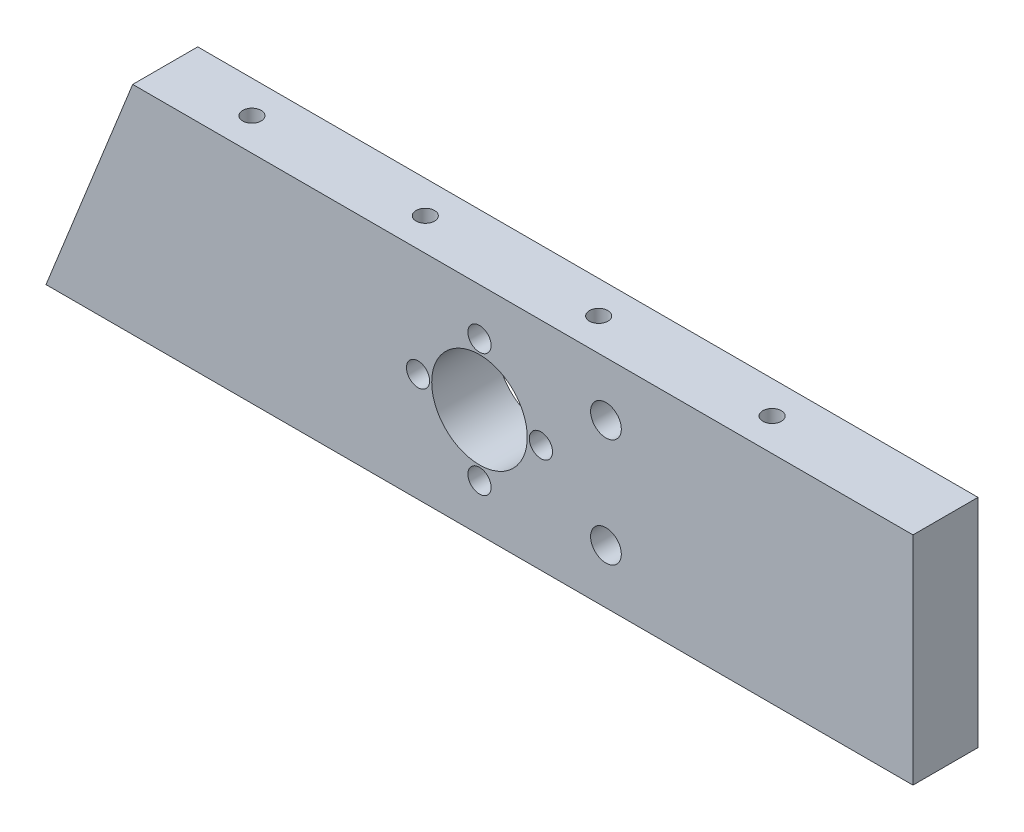
SolidWorks part; units mm, degrees
material "PE High Density"
ref_plane "Front Plane" through (0, 0, 0) normal (0, 0, 1) x (1, 0, 0)
ref_plane "Top Plane" through (0, 0, 0) normal (0, 1, 0) x (1, 0, 0)
ref_plane "Right Plane" through (0, 0, 0) normal (1, 0, 0) x (0, 0, -1)
sketch "Sketch1" plane through (0, 0, 0) normal (0, 0, 1) x (1, 0, 0)
  line L1 (-50.8, 15.875) -> (63.5, 15.875)
  line L2 (-50.8, 15.875) -> (-63.5, -15.875)
  line L3 (-63.5, -15.875) -> (63.5, -15.875)
  line L4 (63.5, 15.875) -> (63.5, -15.875)
  line L5 (18.525, 15.875) -> (18.525, -15.875) construction
  line L6 (63.5, 0) -> (-57.15, 0) construction
  circle A0 centre (0, -9) radius 1.7
  circle A1 centre (-9, 0) radius 1.7
  circle A2 centre (0, 9) radius 1.7
  circle A3 centre (9, 0) radius 1.7
  arc A8 (-5.3578, -2.967) -> (-5.3172, -2.9531) centre (-6.35, 0) ccw construction
  circle A16 centre (0, 0) radius 7
  circle A17 centre (0, 0) radius 9 construction
  circle A18 centre (18.525, 7.9375) radius 2.2479
  circle A19 centre (18.525, -7.9375) radius 2.2479
  point P0 (0, 0)
  point P17 (0, 0)
  dimension "D3" = 3.4
  dimension "D5" = 14
  dimension "D7" = 4.4958
  dimension "D1" = 127
  dimension "D2" = 31.75
  dimension "D8" = 114.3
  dimension "D11" = 9
  dimension "D4" = 63.5
  dimension "D9" = 7.9375
  dimension "D6" = 9.525
extrude "Boss-Extrude1" add sketch "Sketch1" along normal blind 9.525
hole_wizard "Tap Drill for #6-32 Tap1" positions "Sketch11" profile "Sketch12" hole size "#6-32" standard "ANSI Inch"
sketch "Sketch11" plane through (0, -15.875, 0) normal (0, -1, 0) x (-1, 0, 0)
  line L0 (-63.5, -9.525) -> (-63.5, 0) construction
  line L1 (63.5, -9.525) -> (-63.5, -9.525) construction
  point P0 (-38.1, -4.7625)
  dimension "D1" = 25.4
  dimension "D2" = 4.7625
sketch "Sketch12" plane through (38.1, -15.875, 4.7625) normal (1, 0, 0) x (0, 0, -1)
  line L0 (0, 0) -> (0, 13.5127)
  line L1 (0, 13.5127) -> (1.3525, 12.7)
  line L2 (1.3525, 12.7) -> (1.3525, 0)
  line L5 (1.3525, 0) -> (0, 0)
  line L10 (0, 13.5127) -> (-1.3526, 12.7) construction
  line L11 (0, -6.35) -> (0, 107.95) construction
  dimension "Hole Dia." = 2.7051
  dimension "Hole Depth" = 12.7
  dimension "Drill Angle" = 118
pattern_linear "LPattern1" count 4 spacing 25.4 along (-1, 0, 0) of "Tap Drill for #6-32 Tap1"
mirror "Mirror8" about plane through (0, 0, 0) normal (0, 1, 0) of "Tap Drill for #6-32 Tap1", "LPattern1"
equation "\"Plate Screw Hole Diameter\"= 0.116in"
equation "\"Plate Width\" = 5in"
equation "\"Plate Thickness\" = 0.375in"
equation "\"Num holes\" = 4"
equation "\"Plate Height\" = 1.25in"
equation "\"D1@Sketch11\"=\"Plate Width\" / ( \"Num holes\" + 1)"
equation "\"D2@Sketch11\"=\"Plate Thickness\"/2"
equation "\"D3@LPattern1\"=\"Plate Width\" / ( \"Num holes\"  + 1 )"
equation "\"D1@Sketch1\"=\"Plate Width\""
equation "\"D2@Sketch1\"=\"Plate Height\""
equation "\"D4@Sketch1\"= \"Plate Width\"/2"
equation "\"Top Plate Width\" = 4.5in"
equation "\"D8@Sketch1\"=\"Top Plate Width\""
equation "\"Plate Clearance Hole Diameter\" = 0.125in"
equation "\"Plate Tap Hole Diameter\" = 0.116in"
equation "\"Bottom Plate Length\" = 6.5in"
equation "\"Number Eight Clearance Size\" = 0.177in"
equation "\"D7@Sketch1\"=\"Number Eight Clearance Size\""
equation "\"D9@Sketch1\"=\"Plate Height\" / 4"
